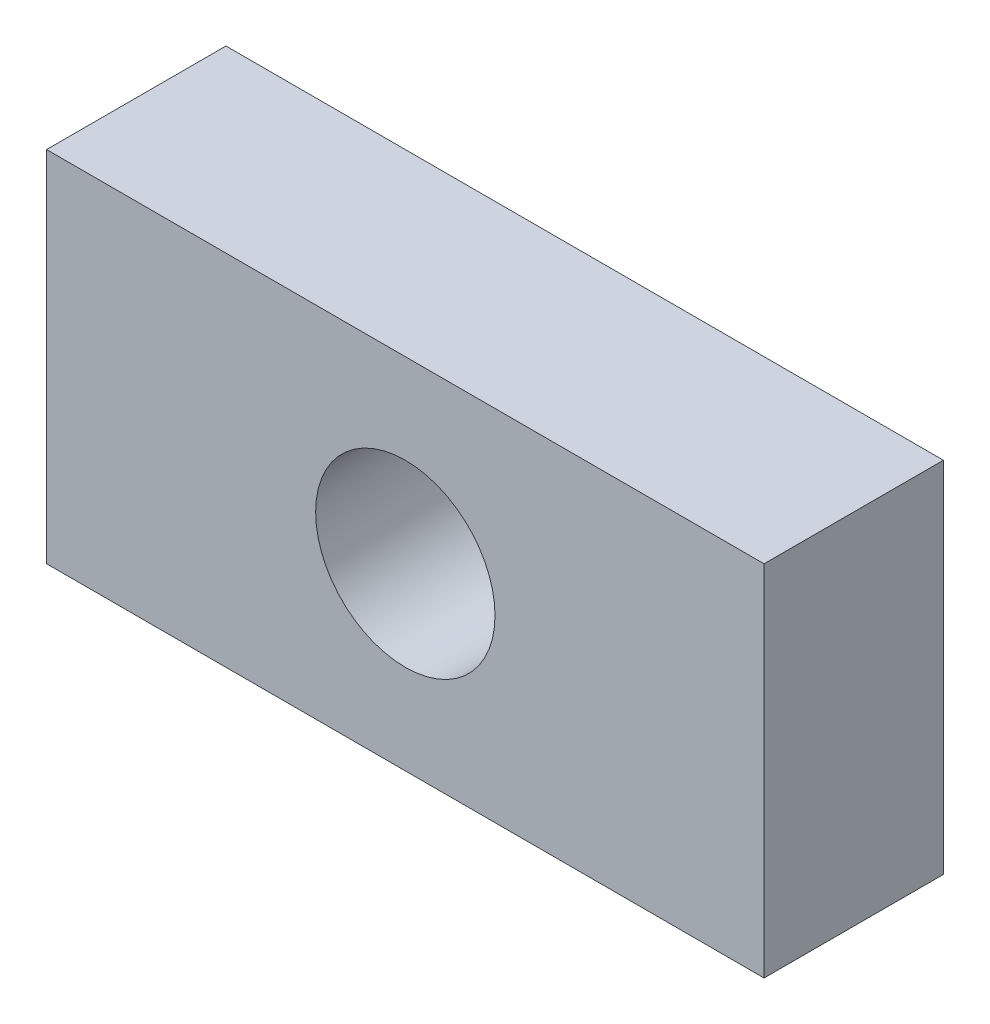
SolidWorks part; units mm, degrees
ref_plane "Front Plane" through (0, 0, 0) normal (0, 0, 1) x (1, 0, 0)
ref_plane "Top Plane" through (0, 0, 0) normal (0, 1, 0) x (1, 0, 0)
ref_plane "Right Plane" through (0, 0, 0) normal (1, 0, 0) x (0, 0, -1)
sketch "Sketch1" plane through (0, 0, 0) normal (0, 0, 1) x (1, 0, 0)
  line L0 (-100, 50) -> (-100, -50)
  line L1 (-100, -50) -> (100, -50)
  line L2 (100, -50) -> (100, 50)
  line L3 (100, 50) -> (-100, 50)
  circle A0 centre (0, 0) radius 25
  dimension "D3" = 50
  dimension "D1" = 200
  dimension "D2" = 100
  dimension "D4" = 100
  dimension "D5" = 50
extrude "Boss-Extrude1" add sketch "Sketch1" along normal blind 50 contours L0 L1 L2 L3
extrude "Cut-Extrude1" cut sketch "Sketch1<3>" along normal through all both and the other way through all contours A0
sketch "Sketch1<3>" plane through (0, 0, 0) normal (0, 0, 1) x (1, 0, 0) same geometry as "Sketch1"
